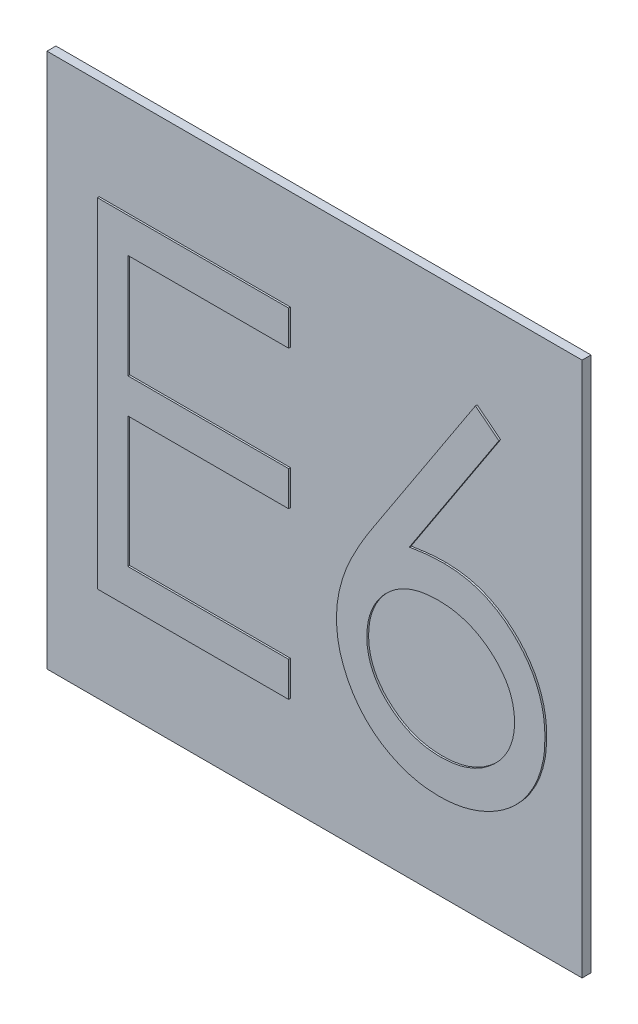
SolidWorks part; units mm, degrees
material "Custom Plastic"
ref_plane "Front Plane" through (0, 0, 0) normal (0, 0, 1) x (1, 0, 0)
ref_plane "Top Plane" through (0, 0, 0) normal (0, 1, 0) x (1, 0, 0)
ref_plane "Right Plane" through (0, 0, 0) normal (1, 0, 0) x (0, 0, -1)
sketch "Sketch1" plane through (0, 0, 0) normal (0, 0, 1) x (1, 0, 0)
  line L1 (0, 0) -> (76.2, 0)
  line L2 (0, 0) -> (0, 76.2)
  line L3 (0, 76.2) -> (76.2, 76.2)
  line L4 (76.2, 0) -> (76.2, 76.2)
  dimension "D1" = 76.2
  dimension "D2" = 76.2
extrude "Boss-Extrude1" add sketch "Sketch1" along normal blind 1.27
sketch "Sketch2" plane through (0, 0, 1.27) normal (0, 0, 1) x (1, 0, 0)
  text T0 "E6" font "Century Gothic" height 48.26
  point P1 (17.426, 15.8224)
  point P2 (0, 10.8993)
  point P3 (0, 0)
extrude "Boss-Extrude2" add sketch "Sketch2" along normal blind 0.254
